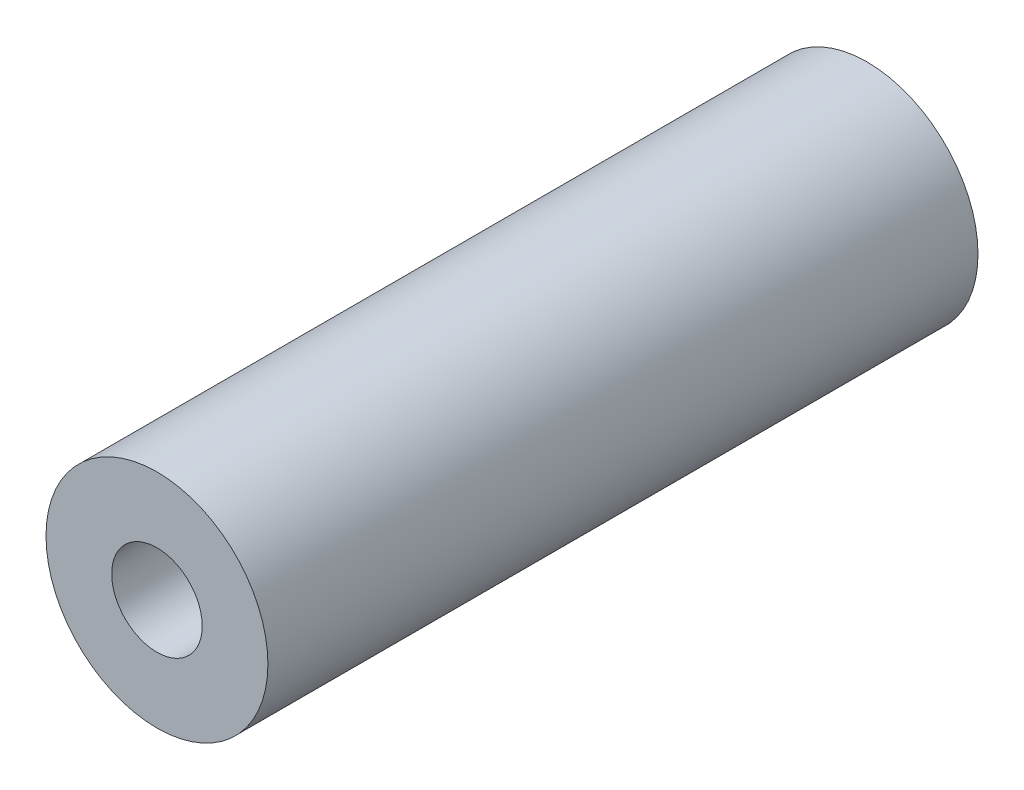
SolidWorks part; units mm, degrees
ref_plane "Front Plane" through (0, 0, 0) normal (0, 0, 1) x (1, 0, 0)
ref_plane "Top Plane" through (0, 0, 0) normal (0, 1, 0) x (1, 0, 0)
ref_plane "Right Plane" through (0, 0, 0) normal (1, 0, 0) x (0, 0, -1)
sketch "Sketch1" plane through (0, 0, 0) normal (0, 0, 1) x (1, 0, 0)
  circle A0 centre (0, 0) radius 7.9375
  circle A1 centre (0, 0) radius 3.2385
  dimension "OD" = 15.875
  dimension "ID" = 6.477
extrude "Extrude1" add sketch "Sketch1" along normal mid plane 50.8
